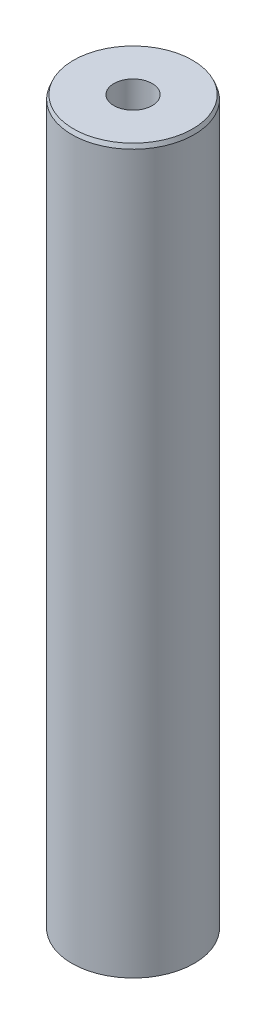
SolidWorks part; units mm, degrees
ref_plane "Front Plane" through (0, 0, 0) normal (0, 0, 1) x (1, 0, 0)
ref_plane "Top Plane" through (0, 0, 0) normal (0, 1, 0) x (1, 0, 0)
ref_plane "Right Plane" through (0, 0, 0) normal (1, 0, 0) x (0, 0, -1)
sketch "Sketch1" plane through (0, 0, 0) normal (0, 1, 0) x (1, 0, 0)
  circle A0 centre (0, 0) radius 12.5
  dimension "SHAFT_OD" = 25
extrude "Boss-Extrude1" add sketch "Sketch1" along normal blind 147.8683
sketch "Sketch2" plane through (0, 0, 0) normal (0, 1, 0) x (1, 0, 0)
  circle A0 centre (0, 0) radius 3.9198
  dimension "BORE_D" = 7.8396
extrude "Cut-Extrude1" cut sketch "Sketch2" along normal through all
chamfer "Chamfer1" distance 0.8463 angle 21.486 2 edges at (0, 147.8683, 12.5) (0, 0, 12.5) first distance on face at (0, 147.8683, 12.5) first distance on face at (0, 0, 3.9198)
